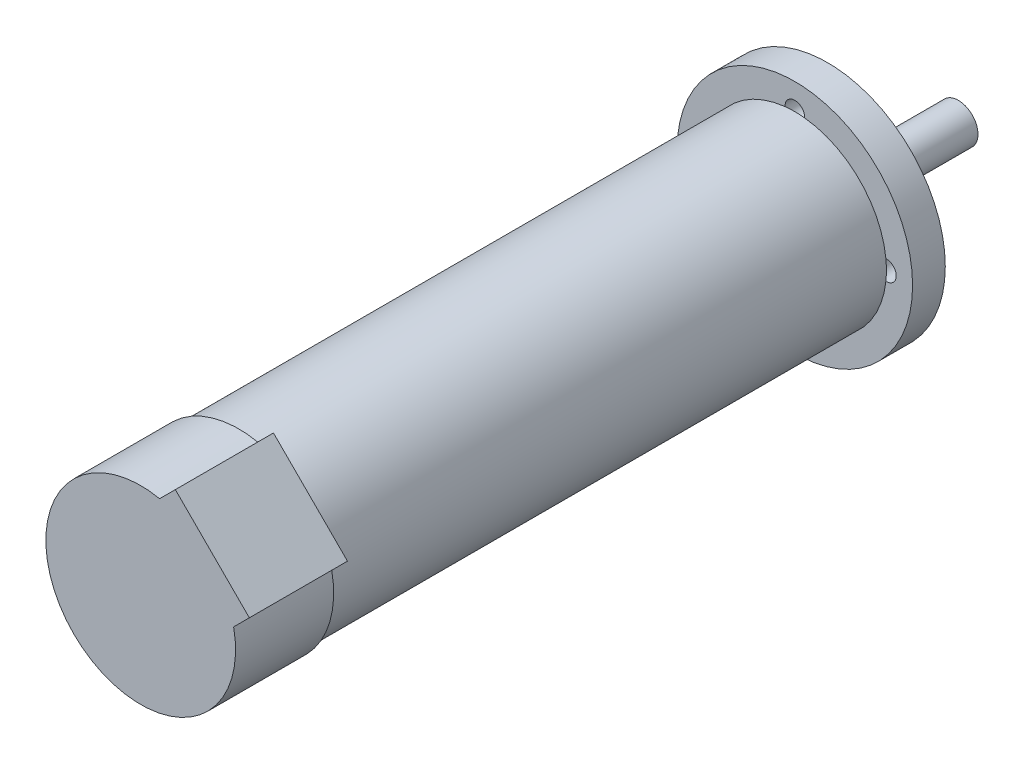
SolidWorks part; units mm, degrees
ref_plane "Front Plane" through (0, 0, 0) normal (0, 0, 1) x (1, 0, 0)
ref_plane "Top Plane" through (0, 0, 0) normal (0, 1, 0) x (1, 0, 0)
ref_plane "Right Plane" through (0, 0, 0) normal (1, 0, 0) x (0, 0, -1)
sketch "Sketch1" plane through (0, 0, 0) normal (0, 0, 1) x (1, 0, 0)
  circle A0 centre (0, 0) radius 18
  dimension "D1" = 36
extrude "Boss-Extrude1" add sketch "Sketch1" along normal blind 5
sketch "Sketch2" plane through (0, 0, 5) normal (0, 0, 1) x (1, 0, 0)
  circle A0 centre (0, 0) radius 14
  dimension "D1" = 28
extrude "Boss-Extrude2" add sketch "Sketch2" along normal blind 100
sketch "Sketch3" plane through (0, 0, 105) normal (0, 0, 1) x (1, 0, 0)
  line L0 (-29.0679, 0) -> (29.0679, 0) construction
  line L1 (2.4672, 13.7809) -> (13.7809, 2.4672) construction
  line L2 (13.7809, 2.4672) -> (16.6093, 5.2956) construction
  line L3 (16.6093, 5.2956) -> (5.2956, 16.6093)
  line L4 (5.2956, 16.6093) -> (2.4672, 13.7809) construction
  line L5 (5.2956, 16.6093) -> (2.8945, 14.2082)
  line L6 (16.6093, 5.2956) -> (14.2082, 2.8945)
  circle A0 centre (0, 0) radius 14 construction
  arc A1 (2.8945, 14.2082) -> (14.2082, 2.8945) centre (0, 0) ccw
  point P4 (0, 0)
  dimension "D4" = 0.5
  dimension "D1" = 45
  dimension "D2" = 16
  dimension "D3" = 4
extrude "Boss-Extrude3" add sketch "Sketch3" against normal blind 15
sketch "Sketch4" plane through (0, 0, 0) normal (0, 0, -1) x (-1, 0, 0)
  line L0 (0, 0) -> (0, -6.3076) construction
  line L1 (0, 0) -> (5.8999, 0) construction
  circle A0 centre (0, 14) radius 1.5
  circle A1 centre (14, 0) radius 1.5
  circle A2 centre (0, -14) radius 1.5
  circle A3 centre (-14, 0) radius 1.5
  dimension "D1" = 3
  dimension "D2" = 28
  dimension "D3" = 28
extrude "Cut-Extrude1" cut sketch "Sketch4" against normal up to surface (5 mm away) up to face at (14, 0, 5)
sketch "Sketch5" plane through (0, 0, 0) normal (0, 0, -1) x (-1, 0, 0)
  circle A0 centre (0, 0) radius 3
  dimension "D1" = 6
extrude "Boss-Extrude4" add sketch "Sketch5" along normal blind 20
